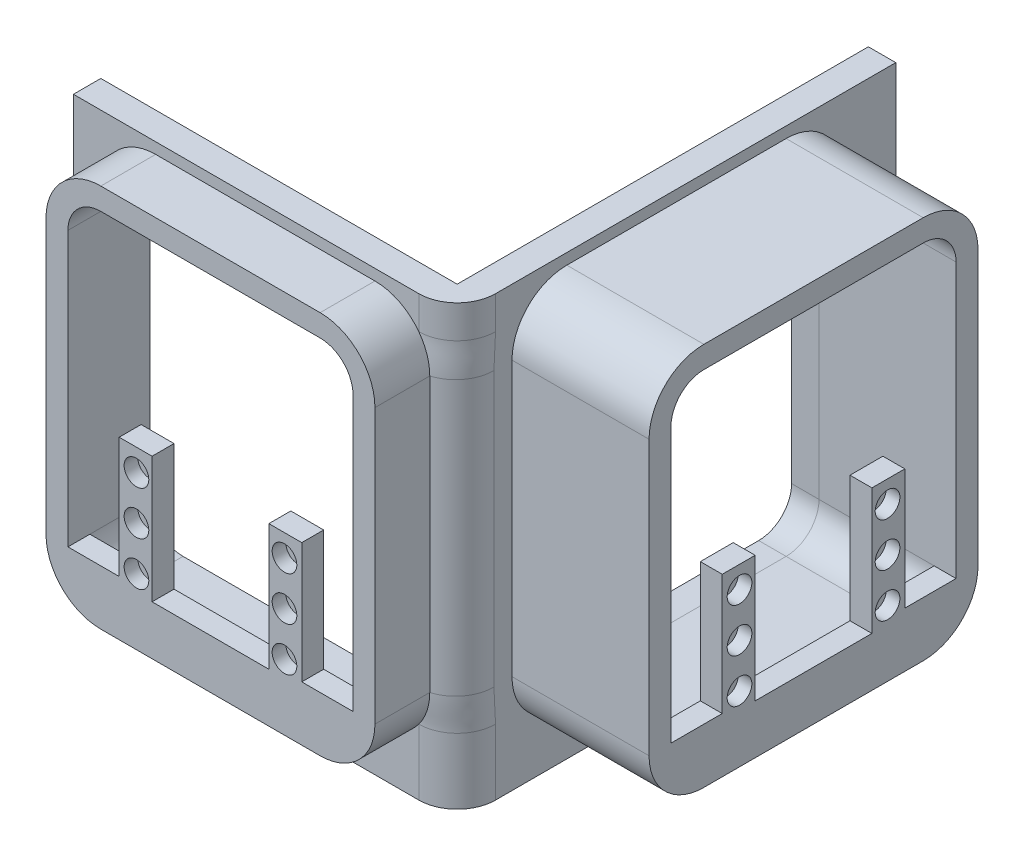
SolidWorks part; units mm, degrees
ref_plane "Front Plane" through (0, 0, 0) normal (0, 0, 1) x (1, 0, 0)
ref_plane "Top Plane" through (0, 0, 0) normal (0, 1, 0) x (1, 0, 0)
ref_plane "Right Plane" through (0, 0, 0) normal (1, 0, 0) x (0, 0, -1)
sketch "Sketch1" plane through (0, 0, 0) normal (0, 0, 1) x (1, 0, 0)
  line L1 (-20, -35) -> (20, -35)
  line L2 (-30, -25) -> (-30, 25)
  line L3 (-20, 35) -> (20, 35)
  line L4 (30, -25) -> (30, 25)
  line L5 (-30, -35) -> (30, 35) construction
  line L6 (-30, 35) -> (30, -35) construction
  arc A1 (20, 35) -> (30, 25) centre (20, 25) cw
  arc A2 (20, -35) -> (30, -25) centre (20, -25) ccw
  arc A3 (-20, -35) -> (-30, -25) centre (-20, -25) cw
  arc A4 (-30, 25) -> (-20, 35) centre (-20, 25) cw
  point P0 (0, 0)
  dimension "D1" = 60
  dimension "D3" = 10
  dimension "D2" = 70
extrude "Boss-Extrude1" add sketch "Sketch1" against normal blind 10
ref_plane "Plane1" through (60, 0, 0) normal (1, 0, 0) x (0, 0, -1)
ref_plane "Plane2" through (60, 0, 0) normal (1, 0, 0) x (0, 0, -1)
sketch "Sketch10" plane through (0, 0, -10) normal (0, 0, -1) x (-1, 0, 0)
  line L0 (0, -3) -> (0, 0) construction
  line L1 (-35, -43) -> (35, -43)
  line L2 (-35, -43) -> (-35, 37)
  line L3 (-35, 37) -> (35, 37)
  line L4 (35, -43) -> (35, 37)
  line L5 (-35, -43) -> (35, 37) construction
  line L6 (-35, 37) -> (35, -43) construction
  point P0 (0, -3)
  dimension "D3" = 3
  dimension "D1" = 80
  dimension "D2" = 70
extrude "Boss-Extrude6" add sketch "Sketch10" along normal blind 80
sketch "Sketch2" plane through (60, 0, 0) normal (1, 0, 0) x (0, 0, -1)
  line L2 (0, 0) -> (146.6861, 0) construction
  line L3 (50, 0) -> (50, 30) construction
  line L5 (10, 37) -> (10, -43) construction
  line L6 (90, 37) -> (90, -43) construction
  line L7 (30, -35) -> (70, -35)
  line L8 (20, -25) -> (20, 25)
  line L9 (30, 35) -> (70, 35)
  line L10 (80, -25) -> (80, 25)
  line L11 (20, -35) -> (80, 35) construction
  line L12 (20, 35) -> (80, -35) construction
  arc A1 (30, -35) -> (20, -25) centre (30, -25) cw
  arc A2 (70, -35) -> (80, -25) centre (70, -25) ccw
  arc A3 (70, 35) -> (80, 25) centre (70, 25) cw
  arc A4 (20, 25) -> (30, 35) centre (30, 25) cw
  dimension "D1" = 60
  dimension "D3" = 10
  dimension "D2" = 70
extrude "Boss-Extrude2" add sketch "Sketch2" against normal up to surface (25 mm away) separate body up to face at (35, -3, -50)
sketch "Sketch11" plane through (0, 37, 0) normal (0, 1, 0) x (1, 0, 0)
  line L1 (-35, 90) -> (30, 90)
  line L2 (-35, 90) -> (-35, 15)
  line L3 (-35, 15) -> (30, 15)
  line L4 (30, 90) -> (30, 15)
  dimension "D1" = 75
  dimension "D2" = 65
extrude "Cut-Extrude5" cut sketch "Sketch11" against normal through all
sketch "Sketch4" plane through (35, 0, 0) normal (-1, 0, 0) x (0, 0, 1)
  line L8 (-70, -31) -> (-30, -31)
  line L9 (-76, 25) -> (-76, -25)
  line L10 (-30, 31) -> (-70, 31)
  line L11 (-24, -25) -> (-24, 25)
  line L12 (-70, -31) -> (-30, -31)
  line L13 (-76, 25) -> (-76, -25)
  line L14 (-30, 31) -> (-70, 31)
  line L15 (-24, -25) -> (-24, 25)
  arc A10 (-76, -25) -> (-70, -31) centre (-70, -25) ccw
  arc A11 (-70, 31) -> (-76, 25) centre (-70, 25) ccw
  arc A12 (-24, 25) -> (-30, 31) centre (-30, 25) ccw
  arc A13 (-30, -31) -> (-24, -25) centre (-30, -25) ccw
  arc A14 (-76, -25) -> (-70, -31) centre (-70, -25) ccw
  arc A15 (-70, 31) -> (-76, 25) centre (-70, 25) ccw
  arc A16 (-24, 25) -> (-30, 31) centre (-30, 25) ccw
  arc A17 (-30, -31) -> (-24, -25) centre (-30, -25) ccw
  dimension "D1" = 4
extrude "Cut-Extrude2" cut sketch "Sketch4" against normal through all contours L12 A17 L15 A16 L14 A15 L13 A14 region at (35, 0, -50)
sketch "Sketch5" plane through (60, 0, 0) normal (1, 0, 0) x (0, 0, -1)
  line L0 (50, 0) -> (50, -31) construction
  line L1 (33.35, -3) -> (39.35, -3)
  line L2 (39.35, -3) -> (39.35, -26)
  line L3 (39.35, -26) -> (60.65, -26)
  line L4 (60.65, -26) -> (60.65, -3)
  line L5 (60.65, -3) -> (66.65, -3)
  line L6 (66.65, -3) -> (66.65, -25)
  line L8 (33.35, -3) -> (33.35, -25)
  line L10 (50, 0) -> (63.5, 0) construction
  line L11 (63.5, 0) -> (63.5, -7) construction
  line L12 (63.5, -7) -> (63.5, -15) construction
  line L13 (63.5, -15) -> (63.5, -23) construction
  line L14 (70, -31) -> (30, -31) construction
  line L15 (30, -31) -> (70, -31)
  line L16 (33.35, -25) -> (24, -25)
  line L17 (66.65, -25) -> (76, -25)
  circle A0 centre (50, 0) radius 11 construction
  arc A1 (24, -25) -> (30, -31) centre (30, -25) ccw construction
  circle A2 centre (63.5, -7) radius 1.25
  arc A3 (24, -25) -> (30, -31) centre (30, -25) ccw
  circle A5 centre (63.5, -15) radius 1.25
  circle A6 centre (63.5, -23) radius 1.25
  circle A7 centre (36.5, -7) radius 1.25
  circle A8 centre (36.5, -15) radius 1.25
  circle A9 centre (36.5, -23) radius 1.25
  arc A10 (70, -31) -> (76, -25) centre (70, -25) ccw
  point P8 (50, -26)
  point P14 (50, -31)
  dimension "D1" = 22
  dimension "D6" = 2.5
  dimension "D3" = 21.3
  dimension "D4" = 13.5
  dimension "D5" = 7
  dimension "D7" = 8
  dimension "D8" = 8
  dimension "D9" = 6
  dimension "D10" = 5
  dimension "D12" = 3
extrude "Boss-Extrude3" add sketch "Sketch5" against normal blind 4
sketch "Sketch13" plane through (35, 0, 0) normal (1, 0, 0) x (0, 0, -1)
  line L4 (24, 25) -> (24, -25)
  line L5 (30, -31) -> (70, -31)
  line L6 (76, -25) -> (76, 25)
  line L7 (70, 31) -> (30, 31)
  line L8 (24, 25) -> (24, -25)
  line L9 (30, -31) -> (70, -31)
  line L10 (76, -25) -> (76, 25)
  line L11 (70, 31) -> (30, 31)
  arc A6 (30, 31) -> (24, 25) centre (30, 25) ccw
  arc A7 (24, -25) -> (30, -31) centre (30, -25) ccw
  arc A8 (70, -31) -> (76, -25) centre (70, -25) ccw
  arc A9 (76, 25) -> (70, 31) centre (70, 25) ccw
  arc A10 (30, 31) -> (24, 25) centre (30, 25) ccw
  arc A11 (24, -25) -> (30, -31) centre (30, -25) ccw
  arc A12 (70, -31) -> (76, -25) centre (70, -25) ccw
  arc A13 (76, 25) -> (70, 31) centre (70, 25) ccw
  dimension "D1" = 0
extrude "Cut-Extrude6" cut sketch "Sketch13" against normal up to surface (5 mm away) up to face at (30, -3, -52.5)
sketch "Sketch14" plane through (0, 0, 0) normal (0, 0, 1) x (1, 0, 0)
  line L8 (20, 31) -> (-20, 31)
  line L9 (26, -25) -> (26, 25)
  line L10 (-20, -31) -> (20, -31)
  line L11 (-26, 25) -> (-26, -25)
  line L12 (20, 31) -> (-20, 31)
  line L13 (26, -25) -> (26, 25)
  line L14 (-20, -31) -> (20, -31)
  line L15 (-26, 25) -> (-26, -25)
  arc A10 (26, 25) -> (20, 31) centre (20, 25) ccw
  arc A11 (20, -31) -> (26, -25) centre (20, -25) ccw
  arc A12 (-26, -25) -> (-20, -31) centre (-20, -25) ccw
  arc A13 (-20, 31) -> (-26, 25) centre (-20, 25) ccw
  arc A14 (26, 25) -> (20, 31) centre (20, 25) ccw
  arc A15 (20, -31) -> (26, -25) centre (20, -25) ccw
  arc A16 (-26, -25) -> (-20, -31) centre (-20, -25) ccw
  arc A17 (-20, 31) -> (-26, 25) centre (-20, 25) ccw
  dimension "D1" = 4
extrude "Cut-Extrude7" cut sketch "Sketch14" against normal up to surface (15 mm away) up to face at (-2.5, -3, -15)
sketch "Sketch15" plane through (0, 0, 0) normal (0, 0, 1) x (1, 0, 0)
  line L0 (0, 0) -> (0, -17.9719) construction
  line L1 (-16.65, -3) -> (-10.65, -3)
  line L2 (-10.65, -3) -> (-10.65, -26)
  line L3 (-10.65, -26) -> (10.65, -26)
  line L4 (10.65, -26) -> (10.65, -3)
  line L5 (10.65, -3) -> (16.65, -3)
  line L6 (16.65, -3) -> (16.65, -25)
  line L8 (-16.65, -3) -> (-16.65, -25)
  line L10 (0, 0) -> (13.5, 0) construction
  line L11 (13.5, 0) -> (13.5, -7) construction
  line L12 (13.5, -7) -> (13.5, -15) construction
  line L13 (13.5, -15) -> (13.5, -23) construction
  line L14 (-20, -31) -> (20, -31) construction
  line L15 (-20, -31) -> (20, -31)
  line L16 (26, -25) -> (16.65, -25)
  line L17 (-26, -25) -> (-16.65, -25)
  circle A0 centre (0, 0) radius 11 construction
  circle A1 centre (13.5, -7) radius 1.25
  circle A3 centre (13.5, -15) radius 1.25
  circle A4 centre (13.5, -23) radius 1.25
  circle A5 centre (-13.5, -7) radius 1.25
  circle A6 centre (-13.5, -15) radius 1.25
  circle A7 centre (-13.5, -23) radius 1.25
  arc A9 (-26, -25) -> (-20, -31) centre (-20, -25) ccw
  arc A10 (26, -25) -> (20, -31) centre (20, -25) cw
  point P5 (0, -26)
  dimension "D1" = 22
  dimension "D5" = 2.5
  dimension "D2" = 21.3
  dimension "D3" = 13.5
  dimension "D4" = 7
  dimension "D6" = 8
  dimension "D7" = 8
  dimension "D8" = 6
  dimension "D9" = 5
  dimension "D10" = 3
extrude "Boss-Extrude7" add sketch "Sketch15" against normal blind 4
sketch "Sketch16" plane through (60, 0, 0) normal (1, 0, 0) x (0, 0, -1)
  circle A0 centre (63.5, -7) radius 2.25
  circle A1 centre (63.5, -15) radius 2.25
  circle A2 centre (63.5, -23) radius 2.25
  circle A3 centre (36.5, -23) radius 2.25
  circle A4 centre (36.5, -15) radius 2.25
  circle A5 centre (36.5, -7) radius 2.25
  dimension "D1" = 4.5
extrude "Cut-Extrude8" cut sketch "Sketch16" against normal blind 2.5
fillet "Fillet1" radius 7 1 edges at (35, -3, -10)
fillet "Fillet2" [suppressed] radius 10
sketch "Sketch17" plane through (0, 0, 0) normal (0, 0, 1) x (1, 0, 0)
  circle A0 centre (-13.5, -7) radius 2.25
  circle A1 centre (-13.5, -15) radius 2.25
  circle A2 centre (-13.5, -23) radius 2.25
  circle A3 centre (13.5, -7) radius 2.25
  circle A4 centre (13.5, -15) radius 2.25
  circle A5 centre (13.5, -23) radius 2.25
  dimension "D1" = 4.5
extrude "Cut-Extrude9" cut sketch "Sketch17" against normal blind 2.5
